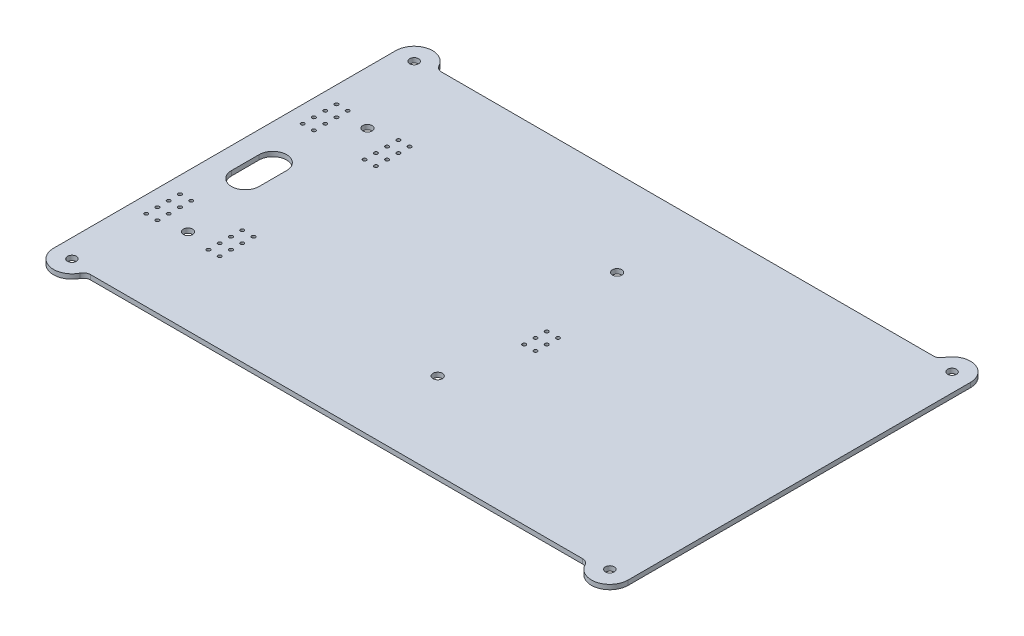
SolidWorks part; units mm, degrees
material "A-Glass Fiber"
ref_plane "Front Plane" through (0, 0, 0) normal (0, 0, 1) x (1, 0, 0)
ref_plane "Top Plane" through (0, 0, 0) normal (0, 1, 0) x (1, 0, 0)
ref_plane "Right Plane" through (0, 0, 0) normal (1, 0, 0) x (0, 0, -1)
sketch "Sketch1" plane through (0, 0, 0) normal (0, 1, 0) x (1, 0, 0)
  line L0 (0, 0) -> (135.8225, 0) construction
  line L2 (-58.612, -57.8993) -> (-58.612, 57.8993)
  line L4 (135.8225, -57.8993) -> (135.8225, 57.8993)
  line L7 (135.8225, 57.9501) -> (135.8225, 66.8401) construction
  line L8 (-44.601, 59.3713) -> (121.8115, 59.3713)
  line L9 (-44.601, -59.3713) -> (121.8115, -59.3713)
  arc A0 (-58.612, 57.8993) -> (-46.8591, 60.7482) centre (-52.3902, 57.8993) cw
  arc A1 (124.0696, 60.7482) -> (135.8225, 57.8993) centre (129.6008, 57.8993) cw
  arc A2 (135.8225, -57.8993) -> (124.0696, -60.7482) centre (129.6008, -57.8993) cw
  arc A3 (-46.8591, -60.7482) -> (-58.612, -57.8993) centre (-52.3902, -57.8993) cw
  arc A4 (-46.8591, -60.7482) -> (-44.601, -59.3713) centre (-44.601, -61.9113) cw
  arc A5 (121.8115, -59.3713) -> (124.0696, -60.7482) centre (121.8115, -61.9113) cw
  arc A6 (124.0696, 60.7482) -> (121.8115, 59.3713) centre (121.8115, 61.9113) cw
  arc A7 (-44.601, 59.3713) -> (-46.8591, 60.7482) centre (-44.601, 61.9113) cw
  arc A8 (31.0353, 66.8607) -> (46.1753, 66.8607) centre (38.6053, 66.9417) ccw construction
  point P1 (0, 0)
  point P8 (11.4228, 0)
  dimension "D1" = 2.54
extrude "Boss-Extrude1" add sketch "Sketch1" against normal blind 1.5875
sketch "Sketch2" plane through (0, 0, 0) normal (0, 1, 0) x (1, 0, 0)
  circle A35 centre (-40.6725, -30.35) radius 1.5875
  circle A36 centre (-40.6725, -30.35) radius 1.5875
  circle A37 centre (-40.6725, 30.35) radius 1.5875
  circle A38 centre (-40.6725, 30.35) radius 1.5875
  circle A39 centre (43.8275, 30.35) radius 1.5875
  circle A40 centre (43.8275, 30.35) radius 1.5875
  circle A41 centre (43.8275, -30.35) radius 1.5875
  circle A42 centre (43.8275, -30.35) radius 1.5875
  dimension "D27" = 0
  dimension "D28" = 0
  dimension "D29" = 0
  dimension "D30" = 0
extrude "Cut-Extrude1" cut sketch "Sketch2" against normal through all
sketch "Sketch3" plane through (0, 0, 0) normal (0, 1, 0) x (1, 0, 0)
  line L5 (-46.6035, 4.285) -> (-46.6035, -5.035) construction
  line L6 (-41.9335, 4.285) -> (-41.9335, -5.035)
  line L7 (-51.2735, 4.285) -> (-51.2735, -5.035)
  line L17 (-43.2035, 3.375) -> (-41.9335, 3.375) construction
  line L18 (-44.8535, 7.2) -> (-44.1998, 8.2889) construction
  line L19 (-46.6035, 7.2) -> (-46.6035, 8.955) construction
  line L20 (-44.8535, 7.2) -> (-48.3535, 7.2) construction
  line L21 (-46.6035, -7.95) -> (-46.6035, -9.705) construction
  line L22 (-48.3535, -7.95) -> (-44.8535, -7.95) construction
  arc A13 (-41.9335, 4.285) -> (-51.2735, 4.285) centre (-46.6035, 4.285) ccw
  arc A14 (-51.2735, -5.035) -> (-41.9335, -5.035) centre (-46.6035, -5.035) ccw
  arc A17 (-44.8535, 0.46) -> (-44.8535, 6.29) centre (-46.6035, 3.375) ccw construction
  point P2 (-46.6035, -0.375)
  dimension "D1" = 1.27
extrude "Cut-Extrude2" cut sketch "Sketch3" against normal through all
sketch "Sketch4" plane through (0, -1.5875, 0) normal (0, -1, 0) x (1, 0, 0)
  line L4 (-34.35, -10.348) -> (-39.27, -10.348)
  line L5 (-34.35, -25.08) -> (-34.35, -10.348)
  line L6 (-39.27, -25.08) -> (-34.35, -25.08)
  line L7 (-39.27, -10.348) -> (-39.27, -25.08)
  line L8 (-34.35, -10.348) -> (-39.27, -10.348)
  line L9 (-34.35, -25.08) -> (-34.35, -10.348)
  line L10 (-39.27, -25.08) -> (-34.35, -25.08)
  line L11 (-39.27, -10.348) -> (-39.27, -25.08)
  line L12 (-34.35, 25.63) -> (-39.27, 25.63)
  line L13 (-34.35, 10.898) -> (-34.35, 25.63)
  line L14 (-39.27, 10.898) -> (-34.35, 10.898)
  line L15 (-39.27, 25.63) -> (-39.27, 10.898)
  line L16 (-34.35, 25.63) -> (-39.27, 25.63)
  line L17 (-34.35, 10.898) -> (-34.35, 25.63)
  line L18 (-39.27, 10.898) -> (-34.35, 10.898)
  line L19 (-39.27, 25.63) -> (-39.27, 10.898)
  line L20 (-44.42, 10.898) -> (-39.5, 10.898)
  line L21 (-39.5, 10.898) -> (-39.5, 25.63)
  line L22 (-39.5, 25.63) -> (-44.42, 25.63)
  line L23 (-44.42, 25.63) -> (-44.42, 10.898)
  line L24 (-44.42, 10.898) -> (-39.5, 10.898)
  line L25 (-39.5, 10.898) -> (-39.5, 25.63)
  line L26 (-39.5, 25.63) -> (-44.42, 25.63)
  line L27 (-44.42, 25.63) -> (-44.42, 10.898)
  line L28 (-39.5, -10.348) -> (-44.42, -10.348)
  line L29 (-39.5, -25.08) -> (-39.5, -10.348)
  line L30 (-44.42, -25.08) -> (-39.5, -25.08)
  line L31 (-44.42, -10.348) -> (-44.42, -25.08)
  line L32 (-39.5, -10.348) -> (-44.42, -10.348)
  line L33 (-39.5, -25.08) -> (-39.5, -10.348)
  line L34 (-44.42, -25.08) -> (-39.5, -25.08)
  line L35 (-44.42, -10.348) -> (-44.42, -25.08)
  line L36 (35.46, 13.148) -> (40.38, 13.148)
  line L37 (35.46, 27.88) -> (35.46, 13.148)
  line L38 (40.38, 27.88) -> (35.46, 27.88)
  line L39 (40.38, 13.148) -> (40.38, 27.88)
  line L40 (35.46, 13.148) -> (40.38, 13.148)
  line L41 (35.46, 27.88) -> (35.46, 13.148)
  line L42 (40.38, 27.88) -> (35.46, 27.88)
  line L43 (40.38, 13.148) -> (40.38, 27.88)
  dimension "D1" = 0
  dimension "D2" = 0
  dimension "D3" = 0
  dimension "D4" = 0
  dimension "D5" = 0
sketch "Sketch6" plane through (0, -1.5875, 0) normal (0, -1, 0) x (1, 0, 0)
  line L0 (-20.19, 27.65) -> (-20.19, 33.65) construction
  line L1 (-20.19, 33.65) -> (-14.19, 33.65) construction
  line L2 (-14.19, 33.65) -> (-14.19, 27.65) construction
  line L3 (-14.19, 27.65) -> (-20.19, 27.65) construction
  line L4 (33.69, -6.45) -> (33.69, -22.45)
  line L5 (54.59, -6.45) -> (33.69, -6.45)
  line L6 (54.59, -22.45) -> (54.59, -6.45)
  line L7 (33.69, -22.45) -> (54.59, -22.45)
  line L8 (33.69, -6.45) -> (33.69, -22.45)
  line L9 (54.59, -6.45) -> (33.69, -6.45)
  line L10 (54.59, -22.45) -> (54.59, -6.45)
  line L11 (33.69, -22.45) -> (54.59, -22.45)
  line L20 (-8.69, 27.65) -> (-8.69, 33.65) construction
  line L21 (-8.69, 33.65) -> (-2.69, 33.65) construction
  line L22 (-2.69, 33.65) -> (-2.69, 27.65) construction
  line L23 (-2.69, 27.65) -> (-8.69, 27.65) construction
  line L24 (-20.19, 27.65) -> (-20.19, 33.65)
  line L25 (-20.19, 33.65) -> (-14.19, 33.65)
  line L26 (-14.19, 33.65) -> (-14.19, 27.65)
  line L27 (-14.19, 27.65) -> (-20.19, 27.65)
  line L28 (-8.69, 27.65) -> (-8.69, 33.65)
  line L29 (-8.69, 33.65) -> (-2.69, 33.65)
  line L30 (-2.69, 33.65) -> (-2.69, 27.65)
  line L31 (-2.69, 27.65) -> (-8.69, 27.65)
  line L80 (55.31, -35.15) -> (55.31, 35.15)
  line L82 (55.31, 35.15) -> (-55.31, 35.15)
  line L84 (-55.31, 35.15) -> (-55.31, -35.15)
  line L86 (-55.31, -35.15) -> (55.31, -35.15)
  line L92 (55.31, -35.15) -> (55.31, 35.15)
  line L94 (55.31, 35.15) -> (-55.31, 35.15)
  line L96 (-55.31, 35.15) -> (-55.31, -35.15)
  line L98 (-55.31, -35.15) -> (55.31, -35.15)
  circle A0 centre (-17.19, 30.65) radius 1.75 construction
  circle A1 centre (-5.69, 30.65) radius 1.75 construction
  circle A2 centre (-17.19, 30.65) radius 1.75
  circle A3 centre (-5.69, 30.65) radius 1.75
  dimension "D1" = 0
  dimension "D2" = 0
sketch "Sketch7" plane through (0, -1.5875, 0) normal (0, -1, 0) x (1, 0, 0)
  circle A1 centre (49.2175, 6.483) radius 0.6
  circle A2 centre (49.2175, 6.483) radius 0.6
  circle A3 centre (-49.1085, -32.125) radius 0.6
  circle A4 centre (-49.1085, -32.125) radius 0.6
  circle A5 centre (-28.1535, -32.125) radius 0.6
  circle A6 centre (-28.1535, -32.125) radius 0.6
  circle A7 centre (-28.1535, 20.707) radius 0.6
  circle A8 centre (-28.1535, 20.707) radius 0.6
  circle A9 centre (-49.2355, 20.707) radius 0.6
  circle A10 centre (-49.2355, 20.707) radius 0.6
  circle A11 centre (-31.9635, 20.707) radius 0.6
  circle A12 centre (-31.9635, 20.707) radius 0.6
  circle A13 centre (-53.0455, 20.707) radius 0.6
  circle A14 centre (-53.0455, 20.707) radius 0.6
  circle A15 centre (-31.9635, 28.327) radius 0.6
  circle A16 centre (-31.9635, 28.327) radius 0.6
  circle A17 centre (-53.0455, 28.327) radius 0.6
  circle A18 centre (-53.0455, 28.327) radius 0.6
  circle A19 centre (-31.9635, 24.517) radius 0.6
  circle A20 centre (-31.9635, 24.517) radius 0.6
  circle A21 centre (-53.0455, 24.517) radius 0.6
  circle A22 centre (-53.0455, 24.517) radius 0.6
  circle A23 centre (-31.9635, -28.315) radius 0.6
  circle A24 centre (-31.9635, -28.315) radius 0.6
  circle A25 centre (-52.9185, -28.315) radius 0.6
  circle A26 centre (-52.9185, -28.315) radius 0.6
  circle A27 centre (-31.9635, -32.125) radius 0.6
  circle A28 centre (-31.9635, -32.125) radius 0.6
  circle A29 centre (-52.9185, -32.125) radius 0.6
  circle A30 centre (-52.9185, -32.125) radius 0.6
  circle A31 centre (-28.1535, 24.517) radius 0.6
  circle A32 centre (-28.1535, 24.517) radius 0.6
  circle A33 centre (-49.2355, 24.517) radius 0.6
  circle A34 centre (-49.2355, 24.517) radius 0.6
  circle A35 centre (-31.9635, 32.137) radius 0.6
  circle A36 centre (-31.9635, 32.137) radius 0.6
  circle A37 centre (-53.0455, 32.137) radius 0.6
  circle A38 centre (-53.0455, 32.137) radius 0.6
  circle A39 centre (-31.9635, -20.695) radius 0.6
  circle A40 centre (-31.9635, -20.695) radius 0.6
  circle A41 centre (-52.9185, -20.695) radius 0.6
  circle A42 centre (-52.9185, -20.695) radius 0.6
  circle A43 centre (-31.9635, -24.505) radius 0.6
  circle A44 centre (-31.9635, -24.505) radius 0.6
  circle A45 centre (-52.9185, -24.505) radius 0.6
  circle A46 centre (-52.9185, -24.505) radius 0.6
  circle A47 centre (-28.1535, 32.137) radius 0.6
  circle A48 centre (-28.1535, 32.137) radius 0.6
  circle A49 centre (-49.2355, 32.137) radius 0.6
  circle A50 centre (-49.2355, 32.137) radius 0.6
  circle A51 centre (-28.1535, 28.327) radius 0.6
  circle A52 centre (-28.1535, 28.327) radius 0.6
  circle A53 centre (-49.2355, 28.327) radius 0.6
  circle A54 centre (-49.2355, 28.327) radius 0.6
  circle A55 centre (-28.1535, -24.505) radius 0.6
  circle A56 centre (-28.1535, -24.505) radius 0.6
  circle A57 centre (-49.1085, -24.505) radius 0.6
  circle A58 centre (-49.1085, -24.505) radius 0.6
  circle A59 centre (-28.1535, -28.315) radius 0.6
  circle A60 centre (-28.1535, -28.315) radius 0.6
  circle A61 centre (-49.1085, -28.315) radius 0.6
  circle A62 centre (-49.1085, -28.315) radius 0.6
  circle A63 centre (49.2175, 2.673) radius 0.6
  circle A64 centre (49.2175, 2.673) radius 0.6
  circle A65 centre (53.0275, -1.137) radius 0.6
  circle A66 centre (53.0275, -1.137) radius 0.6
  circle A67 centre (53.0275, 2.673) radius 0.6
  circle A68 centre (53.0275, 2.673) radius 0.6
  circle A69 centre (53.0275, 6.483) radius 0.6
  circle A70 centre (53.0275, 6.483) radius 0.6
  circle A71 centre (-28.1535, -20.695) radius 0.6
  circle A72 centre (-28.1535, -20.695) radius 0.6
  circle A73 centre (-49.1085, -20.695) radius 0.6
  circle A74 centre (-49.1085, -20.695) radius 0.6
  circle A75 centre (49.2175, -1.137) radius 0.6
  circle A76 centre (49.2175, -1.137) radius 0.6
  dimension "D1" = 0
  dimension "D2" = 0
  dimension "D3" = 0
  dimension "D4" = 0
  dimension "D5" = 0
  dimension "D6" = 0
  dimension "D7" = 0
  dimension "D8" = 0
  dimension "D9" = 0
  dimension "D10" = 0
  dimension "D11" = 0
  dimension "D12" = 0
  dimension "D13" = 0
  dimension "D14" = 0
  dimension "D15" = 0
  dimension "D16" = 0
  dimension "D17" = 0
  dimension "D18" = 0
  dimension "D19" = 0
  dimension "D20" = 0
  dimension "D21" = 0
  dimension "D22" = 0
  dimension "D23" = 0
  dimension "D24" = 0
  dimension "D25" = 0
  dimension "D26" = 0
  dimension "D27" = 0
  dimension "D28" = 0
  dimension "D29" = 0
  dimension "D30" = 0
  dimension "D31" = 0
  dimension "D32" = 0
  dimension "D33" = 0
  dimension "D34" = 0
  dimension "D35" = 0
  dimension "D36" = 0
  dimension "D37" = 0
  dimension "D38" = 0
extrude "Cut-Extrude3" cut sketch "Sketch7" against normal through all
sketch "Sketch8" plane through (0, -1.5875, 0) normal (0, -1, 0) x (1, 0, 0)
  line L4 (-47.9085, -18.395) -> (-54.7585, -18.395)
  line L5 (-47.9085, -34.425) -> (-47.9085, -18.395)
  line L6 (-54.7585, -34.425) -> (-47.9085, -34.425)
  line L7 (-54.7585, -18.395) -> (-54.7585, -34.425)
  line L8 (-47.9085, -18.395) -> (-54.7585, -18.395)
  line L9 (-47.9085, -34.425) -> (-47.9085, -18.395)
  line L10 (-54.7585, -34.425) -> (-47.9085, -34.425)
  line L11 (-54.7585, -18.395) -> (-54.7585, -34.425)
  line L12 (-54.8855, 18.407) -> (-48.0355, 18.407)
  line L13 (-48.0355, 18.407) -> (-48.0355, 34.437)
  line L14 (-48.0355, 34.437) -> (-54.8855, 34.437)
  line L15 (-54.8855, 34.437) -> (-54.8855, 18.407)
  line L16 (-54.8855, 18.407) -> (-48.0355, 18.407)
  line L17 (-48.0355, 18.407) -> (-48.0355, 34.437)
  line L18 (-48.0355, 34.437) -> (-54.8855, 34.437)
  line L19 (-54.8855, 34.437) -> (-54.8855, 18.407)
  line L20 (-33.8035, -18.395) -> (-33.8035, -34.425)
  line L21 (-33.8035, -34.425) -> (-26.9535, -34.425)
  line L22 (-26.9535, -34.425) -> (-26.9535, -18.395)
  line L23 (-26.9535, -18.395) -> (-33.8035, -18.395)
  line L24 (-33.8035, -18.395) -> (-33.8035, -34.425)
  line L25 (-33.8035, -34.425) -> (-26.9535, -34.425)
  line L26 (-26.9535, -34.425) -> (-26.9535, -18.395)
  line L27 (-26.9535, -18.395) -> (-33.8035, -18.395)
  line L28 (-26.9535, 34.437) -> (-33.8035, 34.437)
  line L29 (-26.9535, 18.407) -> (-26.9535, 34.437)
  line L30 (-33.8035, 18.407) -> (-26.9535, 18.407)
  line L31 (-33.8035, 34.437) -> (-33.8035, 18.407)
  line L32 (-26.9535, 34.437) -> (-33.8035, 34.437)
  line L33 (-26.9535, 18.407) -> (-26.9535, 34.437)
  line L34 (-33.8035, 18.407) -> (-26.9535, 18.407)
  line L35 (-33.8035, 34.437) -> (-33.8035, 18.407)
  line L36 (47.8175, 8.783) -> (47.8175, -3.437)
  line L37 (47.8175, -3.437) -> (54.6675, -3.437)
  line L38 (54.6675, -3.437) -> (54.6675, 8.783)
  line L39 (54.6675, 8.783) -> (47.8175, 8.783)
  line L40 (47.8175, 8.783) -> (47.8175, -3.437)
  line L41 (47.8175, -3.437) -> (54.6675, -3.437)
  line L42 (54.6675, -3.437) -> (54.6675, 8.783)
  line L43 (54.6675, 8.783) -> (47.8175, 8.783)
  dimension "D1" = 0
  dimension "D2" = 0
  dimension "D3" = 0
  dimension "D4" = 0
  dimension "D5" = 0
sketch "Sketch9" plane through (0, 0, 0) normal (0, 1, 0) x (1, 0, 0)
  circle A0 centre (-52.3902, 57.8993) radius 1.5
  circle A1 centre (-52.3902, -57.8993) radius 1.5
  circle A2 centre (129.6008, 57.8993) radius 1.5
  circle A3 centre (129.6008, -57.8993) radius 1.5
  dimension "D1" = 3
extrude "Cut-Extrude4" cut sketch "Sketch9" against normal through all
sketch "Sketch11" plane through (0, -1.5875, 0) normal (0, -1, 0) x (1, 0, 0)
  line L0 (140.0242, 31.6837) -> (152.7242, 31.6837) construction
  line L1 (140.0242, 31.6837) -> (152.7242, 31.6837)
sketch "Sketch12" plane through (0, -1.5875, 0) normal (0, -1, 0) x (1, 0, 0)
  circle A0 centre (-40.6725, -30.35) radius 3.81
  circle A1 centre (-40.6725, -30.35) radius 1.5875 construction
  circle A2 centre (-40.6725, 30.35) radius 3.81
  circle A3 centre (43.8275, 30.35) radius 3.81
  circle A4 centre (43.8275, -30.35) radius 3.81
  dimension "D1" = 7.62
sketch "Sketch14" plane through (0, -1.5875, 0) normal (0, -1, 0) x (1, 0, 0)
  line L3 (125.6585, 59.0931) -> (123.9874, 59.0931)
  line L4 (123.9874, 59.0931) -> (123.9874, 56.5531)
  line L5 (123.9874, 56.5531) -> (125.6585, 56.5531)
  line L6 (125.6585, 59.0931) -> (123.9874, 59.0931)
  line L7 (123.9874, 59.0931) -> (123.9874, 56.5531)
  line L8 (123.9874, 56.5531) -> (125.6585, 56.5531)
  line L9 (132.9843, 56.5531) -> (134.6554, 56.5531)
  line L10 (134.6554, 56.5531) -> (134.6554, 59.0931)
  line L11 (134.6554, 59.0931) -> (132.9843, 59.0931)
  line L12 (132.9843, 56.5531) -> (134.6554, 56.5531)
  line L13 (134.6554, 56.5531) -> (134.6554, 59.0931)
  line L14 (134.6554, 59.0931) -> (132.9843, 59.0931)
  line L15 (128.0514, 54.1602) -> (128.0514, 52.4891)
  line L16 (128.0514, 52.4891) -> (130.5914, 52.4891)
  line L17 (130.5914, 52.4891) -> (130.5914, 54.1602)
  line L18 (128.0514, 54.1602) -> (128.0514, 52.4891)
  line L19 (128.0514, 52.4891) -> (130.5914, 52.4891)
  line L20 (130.5914, 52.4891) -> (130.5914, 54.1602)
  line L21 (125.6585, -56.5531) -> (123.9874, -56.5531)
  line L22 (123.9874, -56.5531) -> (123.9874, -59.0931)
  line L23 (123.9874, -59.0931) -> (125.6585, -59.0931)
  line L24 (125.6585, -56.5531) -> (123.9874, -56.5531)
  line L25 (123.9874, -56.5531) -> (123.9874, -59.0931)
  line L26 (123.9874, -59.0931) -> (125.6585, -59.0931)
  line L27 (130.5914, 63.1571) -> (128.0514, 63.1571)
  line L28 (128.0514, 63.1571) -> (128.0514, 61.486)
  line L29 (130.5914, 61.486) -> (130.5914, 63.1571)
  line L30 (130.5914, 63.1571) -> (128.0514, 63.1571)
  line L31 (128.0514, 63.1571) -> (128.0514, 61.486)
  line L32 (130.5914, 61.486) -> (130.5914, 63.1571)
  line L33 (130.5914, -54.1602) -> (130.5914, -52.4891)
  line L34 (130.5914, -52.4891) -> (128.0514, -52.4891)
  line L35 (128.0514, -52.4891) -> (128.0514, -54.1602)
  line L36 (130.5914, -54.1602) -> (130.5914, -52.4891)
  line L37 (130.5914, -52.4891) -> (128.0514, -52.4891)
  line L38 (128.0514, -52.4891) -> (128.0514, -54.1602)
  line L39 (128.0514, -61.486) -> (128.0514, -63.1571)
  line L40 (128.0514, -63.1571) -> (130.5914, -63.1571)
  line L41 (130.5914, -63.1571) -> (130.5914, -61.486)
  line L42 (128.0514, -61.486) -> (128.0514, -63.1571)
  line L43 (128.0514, -63.1571) -> (130.5914, -63.1571)
  line L44 (130.5914, -63.1571) -> (130.5914, -61.486)
  line L45 (134.6554, -59.0931) -> (134.6554, -56.5531)
  line L46 (132.9843, -59.0931) -> (134.6554, -59.0931)
  line L47 (134.6554, -56.5531) -> (132.9843, -56.5531)
  line L48 (134.6554, -59.0931) -> (134.6554, -56.5531)
  line L49 (132.9843, -59.0931) -> (134.6554, -59.0931)
  line L50 (134.6554, -56.5531) -> (132.9843, -56.5531)
  line L51 (-55.7737, -56.5531) -> (-57.4448, -56.5531)
  line L52 (-57.4448, -56.5531) -> (-57.4448, -59.0931)
  line L53 (-57.4448, -59.0931) -> (-55.7737, -59.0931)
  line L54 (-55.7737, -56.5531) -> (-57.4448, -56.5531)
  line L55 (-57.4448, -56.5531) -> (-57.4448, -59.0931)
  line L56 (-57.4448, -59.0931) -> (-55.7737, -59.0931)
  line L57 (-48.4479, -59.0931) -> (-46.7768, -59.0931)
  line L58 (-46.7768, -59.0931) -> (-46.7768, -56.5531)
  line L59 (-46.7768, -56.5531) -> (-48.4479, -56.5531)
  line L60 (-48.4479, -59.0931) -> (-46.7768, -59.0931)
  line L61 (-46.7768, -59.0931) -> (-46.7768, -56.5531)
  line L62 (-46.7768, -56.5531) -> (-48.4479, -56.5531)
  line L63 (-53.3808, -63.1571) -> (-50.8408, -63.1571)
  line L64 (-50.8408, -63.1571) -> (-50.8408, -61.486)
  line L65 (-53.3808, -61.486) -> (-53.3808, -63.1571)
  line L66 (-53.3808, -63.1571) -> (-50.8408, -63.1571)
  line L67 (-50.8408, -63.1571) -> (-50.8408, -61.486)
  line L68 (-53.3808, -61.486) -> (-53.3808, -63.1571)
  line L69 (-50.8408, -54.1602) -> (-50.8408, -52.4891)
  line L70 (-50.8408, -52.4891) -> (-53.3808, -52.4891)
  line L71 (-53.3808, -52.4891) -> (-53.3808, -54.1602)
  line L72 (-50.8408, -54.1602) -> (-50.8408, -52.4891)
  line L73 (-50.8408, -52.4891) -> (-53.3808, -52.4891)
  line L74 (-53.3808, -52.4891) -> (-53.3808, -54.1602)
  line L75 (-50.8408, 61.486) -> (-50.8408, 63.1571)
  line L76 (-50.8408, 63.1571) -> (-53.3808, 63.1571)
  line L77 (-53.3808, 63.1571) -> (-53.3808, 61.486)
  line L78 (-50.8408, 61.486) -> (-50.8408, 63.1571)
  line L79 (-50.8408, 63.1571) -> (-53.3808, 63.1571)
  line L80 (-53.3808, 63.1571) -> (-53.3808, 61.486)
  line L81 (-46.7768, 56.5531) -> (-46.7768, 59.0931)
  line L82 (-48.4479, 56.5531) -> (-46.7768, 56.5531)
  line L83 (-46.7768, 59.0931) -> (-48.4479, 59.0931)
  line L84 (-46.7768, 56.5531) -> (-46.7768, 59.0931)
  line L85 (-48.4479, 56.5531) -> (-46.7768, 56.5531)
  line L86 (-46.7768, 59.0931) -> (-48.4479, 59.0931)
  line L87 (-53.3808, 54.1602) -> (-53.3808, 52.4891)
  line L88 (-53.3808, 52.4891) -> (-50.8408, 52.4891)
  line L89 (-50.8408, 52.4891) -> (-50.8408, 54.1602)
  line L90 (-53.3808, 54.1602) -> (-53.3808, 52.4891)
  line L91 (-53.3808, 52.4891) -> (-50.8408, 52.4891)
  line L92 (-50.8408, 52.4891) -> (-50.8408, 54.1602)
  line L93 (-57.4448, 59.0931) -> (-57.4448, 56.5531)
  line L94 (-57.4448, 56.5531) -> (-55.7737, 56.5531)
  line L95 (-55.7737, 59.0931) -> (-57.4448, 59.0931)
  line L96 (-57.4448, 59.0931) -> (-57.4448, 56.5531)
  line L97 (-57.4448, 56.5531) -> (-55.7737, 56.5531)
  line L98 (-55.7737, 59.0931) -> (-57.4448, 59.0931)
  circle A1 centre (-44.2368, 19.5199) radius 3.8735
  circle A2 centre (-44.2368, 19.5199) radius 3.8735
  circle A3 centre (-44.2368, -19.5199) radius 3.8735
  circle A4 centre (-44.2368, -19.5199) radius 3.8735
  circle A5 centre (121.4474, -19.5199) radius 3.8735
  circle A6 centre (121.4474, -19.5199) radius 3.8735
  circle A7 centre (121.4474, 19.5199) radius 3.8735
  circle A8 centre (121.4474, 19.5199) radius 3.8735
  circle A9 centre (129.3214, -57.8231) radius 3.8735
  circle A10 centre (129.3214, -57.8231) radius 3.8735
  circle A11 centre (129.3214, 57.8231) radius 3.8735
  circle A12 centre (129.3214, 57.8231) radius 3.8735
  arc A13 (125.6585, 59.0931) -> (125.6585, 56.5531) centre (129.3214, 57.8231) ccw
  arc A14 (125.6585, 59.0931) -> (125.6585, 56.5531) centre (129.3214, 57.8231) ccw
  arc A15 (132.9843, 56.5531) -> (132.9843, 59.0931) centre (129.3214, 57.8231) ccw
  arc A16 (132.9843, 56.5531) -> (132.9843, 59.0931) centre (129.3214, 57.8231) ccw
  circle A17 centre (-52.1108, 57.8231) radius 3.8735
  circle A18 centre (-52.1108, 57.8231) radius 3.8735
  circle A19 centre (-52.1108, -57.8231) radius 3.8735
  circle A20 centre (-52.1108, -57.8231) radius 3.8735
  arc A21 (128.0514, 54.1602) -> (130.5914, 54.1602) centre (129.3214, 57.8231) ccw
  arc A22 (128.0514, 54.1602) -> (130.5914, 54.1602) centre (129.3214, 57.8231) ccw
  arc A23 (125.6585, -56.5531) -> (125.6585, -59.0931) centre (129.3214, -57.8231) ccw
  arc A24 (125.6585, -56.5531) -> (125.6585, -59.0931) centre (129.3214, -57.8231) ccw
  arc A25 (130.5914, 61.486) -> (128.0514, 61.486) centre (129.3214, 57.8231) ccw
  arc A26 (130.5914, 61.486) -> (128.0514, 61.486) centre (129.3214, 57.8231) ccw
  arc A27 (130.5914, -54.1602) -> (128.0514, -54.1602) centre (129.3214, -57.8231) ccw
  arc A28 (130.5914, -54.1602) -> (128.0514, -54.1602) centre (129.3214, -57.8231) ccw
  arc A29 (128.0514, -61.486) -> (130.5914, -61.486) centre (129.3214, -57.8231) ccw
  arc A30 (128.0514, -61.486) -> (130.5914, -61.486) centre (129.3214, -57.8231) ccw
  arc A31 (132.9843, -59.0931) -> (132.9843, -56.5531) centre (129.3214, -57.8231) ccw
  arc A32 (132.9843, -59.0931) -> (132.9843, -56.5531) centre (129.3214, -57.8231) ccw
  arc A33 (-55.7737, -56.5531) -> (-55.7737, -59.0931) centre (-52.1108, -57.8231) ccw
  arc A34 (-55.7737, -56.5531) -> (-55.7737, -59.0931) centre (-52.1108, -57.8231) ccw
  arc A35 (-48.4479, -59.0931) -> (-48.4479, -56.5531) centre (-52.1108, -57.8231) ccw
  arc A36 (-48.4479, -59.0931) -> (-48.4479, -56.5531) centre (-52.1108, -57.8231) ccw
  arc A37 (-53.3808, -61.486) -> (-50.8408, -61.486) centre (-52.1108, -57.8231) ccw
  arc A38 (-53.3808, -61.486) -> (-50.8408, -61.486) centre (-52.1108, -57.8231) ccw
  arc A39 (-50.8408, -54.1602) -> (-53.3808, -54.1602) centre (-52.1108, -57.8231) ccw
  arc A40 (-50.8408, -54.1602) -> (-53.3808, -54.1602) centre (-52.1108, -57.8231) ccw
  arc A41 (-50.8408, 61.486) -> (-53.3808, 61.486) centre (-52.1108, 57.8231) ccw
  arc A42 (-50.8408, 61.486) -> (-53.3808, 61.486) centre (-52.1108, 57.8231) ccw
  arc A43 (-48.4479, 56.5531) -> (-48.4479, 59.0931) centre (-52.1108, 57.8231) ccw
  arc A44 (-48.4479, 56.5531) -> (-48.4479, 59.0931) centre (-52.1108, 57.8231) ccw
  arc A45 (-53.3808, 54.1602) -> (-50.8408, 54.1602) centre (-52.1108, 57.8231) ccw
  arc A46 (-53.3808, 54.1602) -> (-50.8408, 54.1602) centre (-52.1108, 57.8231) ccw
  arc A47 (-55.7737, 59.0931) -> (-55.7737, 56.5531) centre (-52.1108, 57.8231) ccw
  arc A48 (-55.7737, 59.0931) -> (-55.7737, 56.5531) centre (-52.1108, 57.8231) ccw
  dimension "D1" = 0
  dimension "D2" = 0
  dimension "D3" = 0
  dimension "D4" = 0
  dimension "D5" = 0
  dimension "D6" = 0
  dimension "D7" = 0
  dimension "D8" = 0
  dimension "D9" = 0
  dimension "D10" = 0
  dimension "D11" = 0
  dimension "D12" = 0
  dimension "D13" = 0
  dimension "D14" = 0
  dimension "D15" = 0
  dimension "D16" = 0
  dimension "D17" = 0
  dimension "D18" = 0
  dimension "D19" = 0
  dimension "D20" = 0
  dimension "D21" = 0
  dimension "D22" = 0
  dimension "D23" = 0
  dimension "D24" = 0
equation "\"62.5mi\"=0.1"
